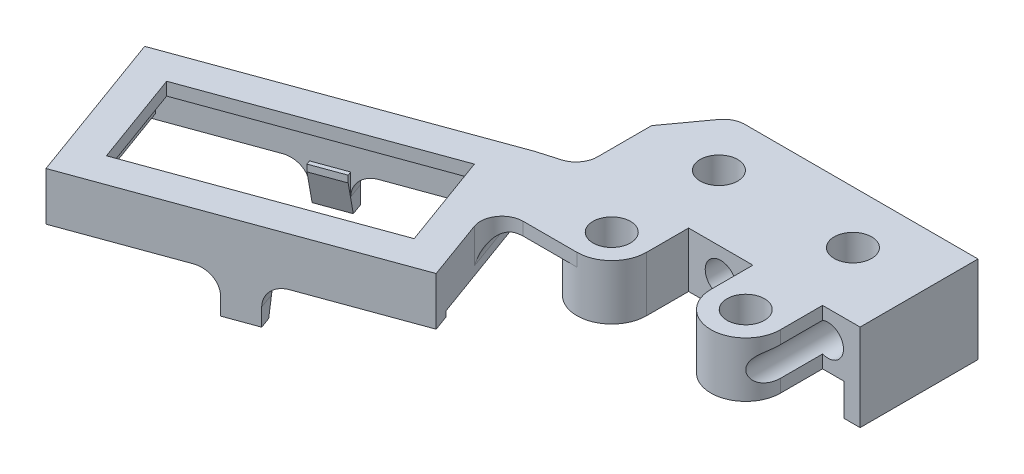
SolidWorks part; units mm, degrees
ref_plane "Front Plane" through (0, 0, 0) normal (0, 0, 1) x (1, 0, 0)
ref_plane "Top Plane" through (0, 0, 0) normal (0, 1, 0) x (1, 0, 0)
ref_plane "Right Plane" through (0, 0, 0) normal (1, 0, 0) x (0, 0, -1)
sketch "Sketch1" plane through (0, 0, 0) normal (0, 1, 0) x (1, 0, 0)
  line L5 (0, 0) -> (16.0528, 0) construction
  line L6 (0, 0) -> (0, -25.9338) construction
  line L7 (-6.25, 5) -> (-6.25, -5) construction
  line L8 (-6.25, 0) -> (0, 0) construction
  line L10 (-13, 9.92) -> (13, 9.92)
  line L11 (-13, 9.92) -> (-13, -9.92)
  line L12 (-13, -9.92) -> (13, -9.92)
  line L13 (13, 9.92) -> (13, -9.92)
  line L14 (-13, 9.92) -> (13, -9.92) construction
  line L15 (-13, -9.92) -> (13, 9.92) construction
  circle A7 centre (-6.25, 5) radius 1.75
  circle A8 centre (-6.25, -5) radius 1.75
  circle A9 centre (6.25, -5) radius 1.75
  circle A10 centre (6.25, 5) radius 1.75
  dimension "D3" = 3.5
  dimension "D4" = 12.5
  dimension "D5" = 10
  dimension "D7" = 26
  dimension "D8" = 4.92
extrude "Boss-Extrude1" add sketch "Sketch1" along normal blind 5.13 contours L13 L10 L11 L12 A9 A8 A7 A10 region at (0, 0, 0)
sketch "Sketch2" plane through (0, 0, 9.92) normal (0, 0, 1) x (1, 0, 0)
  line L0 (-13, 2.565) -> (13, 2.565) construction
  line L1 (-13, 5.13) -> (-13, 0) construction
  line L2 (13, 5.13) -> (13, 0) construction
  line L3 (0, 0) -> (0, 5.13) construction
  line L4 (-13, 5.13) -> (13, 5.13) construction
  circle A0 centre (0, 2.565) radius 1.45
  circle A1 centre (-10, 2.565) radius 1.45
  circle A2 centre (10, 2.565) radius 1.45
  dimension "D1" = 2.9
  dimension "D2" = 10
extrude "Cut-Extrude1" cut sketch "Sketch2" against normal up to next
sketch "Sketch3" plane through (0, 0, 0) normal (0, -1, 0) x (1, 0, 0)
  line L6 (-11.035, -9.92) -> (11.035, -9.92)
  line L7 (0, -9.92) -> (0, 3.71) construction
  line L8 (-13, -9.92) -> (13, -9.92) construction
  line L9 (-11.63, 3.71) -> (11.63, 3.71)
  line L10 (0, 3.71) -> (0, -9.92) construction
  line L11 (11.035, -9.92) -> (11.63, 3.71)
  line L12 (-11.035, -9.92) -> (-11.63, 3.71)
  line L13 (-10.92, 6.04) -> (10.92, 6.04)
  line L14 (0, 6.04) -> (0, -9.92) construction
  line L15 (-7.625, 12.72) -> (7.625, 12.72)
  line L16 (0, 12.72) -> (0, -9.92) construction
  line L17 (-7.625, 12.72) -> (-10.92, 6.04)
  line L18 (10.92, 6.04) -> (7.625, 12.72)
  line L19 (-9.0061, 9.92) -> (9.0061, 9.92)
  line L20 (-13, 9.92) -> (13, 9.92) construction
  line L22 (-13, 9.92) -> (13, 9.92)
  line L23 (-13, 9.92) -> (-13, -9.92)
  line L24 (-13, -9.92) -> (13, -9.92)
  line L25 (13, 9.92) -> (13, -9.92)
  spline S0 degree 2 poles (-11.63, 3.71) (-10.5122, 4.4663) (-10.92, 6.04) knots 0 0 0 1 1 1
  spline S1 degree 2 poles (11.63, 3.71) (10.5122, 4.4663) (10.92, 6.04) knots 0 0 0 1 1 1
  line M4 (13, -9.92) -> (13, 9.92)
  line M5 (13, 9.92) -> (-13, 9.92)
  line M6 (-13, 9.92) -> (-13, -9.92)
  line M7 (-13, -9.92) -> (13, -9.92)
  dimension "D8" = 22.07
  dimension "D9" = 23.26
  dimension "D11" = 13.63
  dimension "D12" = 21.84
  dimension "D14" = 2.33
  dimension "D15" = 15.25
  dimension "D17" = 6.68
extrude "Boss-Extrude2" add sketch "Sketch3" along normal blind 3 contours L12 S0 L17 M5 M6 M7 | S1 L11 L18 M7 M4 M5 region at (-11.9178, 0, 1.0165) region at (11.9178, 0, 1.0165)
sketch "Sketch4" plane through (0, -3, 0) normal (0, -1, 0) x (1, 0, 0)
  line L0 (-13, 1.08) -> (13, 1.08)
  line L1 (-13, 9.92) -> (-13, -9.92) construction
  line L2 (13, -9.92) -> (13, 9.92) construction
  line L3 (-9.5, 5) -> (-9.5, 1.08)
  line L4 (-11.035, -9.92) -> (11.035, -9.92) construction
  line L5 (-3, 5) -> (-3, 1.08)
  line L6 (3, 5) -> (3, 1.08)
  line L7 (9.5, 5) -> (9.5, 1.08)
  line L8 (-13, 1.08) -> (-13, 9.92)
  line L9 (-13, 9.92) -> (13, 9.92)
  line L10 (13, 9.92) -> (13, 1.08)
  circle A0 centre (-6.25, 5) radius 3.25
  circle A1 centre (-6.25, 5) radius 1.75 construction
  circle A2 centre (6.25, 5) radius 3.25
  spline M1 degree 2 poles (10.92, 6.04) (10.5122, 4.4663) (11.63, 3.71) knots 0 0 0 1 1 1
  line M2 (11.63, 3.71) -> (11.035, -9.92)
  line M4 (13, -9.92) -> (13, 9.92)
  line M5 (13, 9.92) -> (9.0061, 9.92)
  line M6 (9.0061, 9.92) -> (10.92, 6.04)
  dimension "D1" = 11
  dimension "D2" = 1.5
extrude "Cut-Extrude2" cut sketch "Sketch4" against normal up to next contours A2 L7 L0 L9 L8 L3 A0 L5 L6 M2 M1 M6 | L0 M2 M4 M5 M6 M1 region at (-1.8909, -3, 6.1294) region at (11.717, -3, 6.3507)
sketch "Sketch5" plane through (0, 5.13, 0) normal (0, 1, 0) x (1, 0, 0)
  line L0 (-18.8665, -2.6039) -> (-10.3647, 9.0978) construction
  line L1 (-18.8665, -2.6039) -> (-10.3647, 9.0978)
  line L2 (-8.7467, 9.9222) -> (-13, 9.92)
  line L3 (-13, 9.92) -> (-13, 5.4706)
  line L4 (-13, 9.92) -> (-13, -1.08) construction
  arc A0 (-8.7467, 9.9222) -> (-10.3647, 9.0978) centre (-8.7467, 7.9222) ccw construction
  arc A1 (-8.7467, 9.9222) -> (-10.3647, 9.0978) centre (-8.7467, 7.9222) ccw
  line M3 (13, 9.92) -> (-13, 9.92)
  line M4 (-13, 9.92) -> (-13, -1.08)
extrude "Cut-Extrude3" cut sketch "Sketch5" against normal up to next contours A1 L1 M3 M4 region at (-11.8764, 5.13, -8.4638)
sketch "Sketch6" plane through (0, 5.13, 0) normal (0, -1, 0) x (1, 0, 0)
  line L0 (-37.7857, 26.2448) -> (-11.0984, 16.5315)
  line L1 (-41.1302, 12.6701) -> (-17.262, 3.9828)
  line L2 (-41.1302, 12.6701) -> (-36.8892, 24.3223)
  line L3 (-36.8892, 24.3223) -> (-13.021, 15.6349)
  line L4 (-17.262, 3.9828) -> (-13.021, 15.6349)
  line L5 (-41.1302, 12.6701) -> (-13.021, 15.6349) construction
  line L6 (-36.8892, 24.3223) -> (-17.262, 3.9828) construction
  line L7 (-16.3655, 2.0602) -> (-11.0984, 16.5315)
  line L8 (-43.0528, 11.7736) -> (-16.3655, 2.0602)
  line L9 (-43.0528, 11.7736) -> (-37.7857, 26.2448)
  line L10 (-6.25, 8.25) -> (-14.1126, 8.25)
  line L11 (-13, 1.08) -> (-32.2548, 1.08) construction
  line L12 (-13, 1.08) -> (-46.0395, 13.1054) construction
  line L14 (-9.5, 5) -> (-9.5, 1.08) construction
  line L15 (-9.5, 5) -> (-9.5, 1.08)
  line L16 (-9.5, 1.08) -> (-13, 1.08)
  line L17 (-13, 1.08) -> (-16.3655, 2.0602)
  arc A0 (-3, 5) -> (-9.5, 5) centre (-6.25, 5) ccw construction
  arc A1 (-3, 5) -> (-9.5, 5) centre (-6.25, 5) ccw
  point P0 (-27.0756, 14.1525)
  dimension "D1" = 12.4
  dimension "D2" = 25.4
  dimension "D4" = 1.27
  dimension "D5" = 20
  dimension "D6" = 10
  dimension "D3" = 1.5
extrude "Boss-Extrude3" add sketch "Sketch6" along normal blind 1.2 contours L9 L8 L1 L2 L3 L4 L7 L0 | L1 L4 L3 L2 | A1 L10 L7 L15 region at (-24.5791, 5.13, 21.0116) region at (-12.1878, 5.13, 4.694) region at (-27.0756, 5.13, 14.1525)
sketch "Sketch9" plane through (0, 3.93, 0) normal (0, -1, 0) x (1, 0, 0)
  line L0 (-43.0528, 11.7736) -> (-37.7857, 26.2448)
  line L1 (-37.7857, 26.2448) -> (-11.0984, 16.5315)
  line L2 (-11.0984, 16.5315) -> (-16.3655, 2.0602)
  line L3 (-14.1126, 8.25) -> (-11.0984, 16.5315) construction
  line L4 (-43.0528, 11.7736) -> (-16.3655, 2.0602)
  line L5 (-43.0528, 11.7736) -> (-16.3655, 2.0602) construction
  line L6 (-41.1302, 12.6701) -> (-17.262, 3.9828)
  line L7 (-13.021, 15.6349) -> (-17.262, 3.9828)
  line L8 (-36.8892, 24.3223) -> (-13.021, 15.6349)
  line L9 (-41.1302, 12.6701) -> (-36.8892, 24.3223)
  dimension "D1" = 1.5
extrude "Boss-Extrude6" add sketch "Sketch9" along normal blind 3.3
sketch "Sketch10" plane through (0, 0.63, 0) normal (0, -1, 0) x (1, 0, 0)
  line L0 (-24.442, 21.3881) -> (-29.7092, 6.9169) construction
  line L1 (-11.0984, 16.5315) -> (-37.7857, 26.2448) construction
  line L2 (-43.0528, 11.7736) -> (-16.3655, 2.0602) construction
  line L3 (-31.1187, 7.4299) -> (-28.2996, 6.4038)
  line L4 (-31.1187, 7.4299) -> (-30.4689, 9.2153)
  line L5 (-28.2996, 6.4038) -> (-27.6498, 8.1893)
  line L6 (-30.4689, 9.2153) -> (-27.6498, 8.1893)
  line L7 (-29.0593, 8.7023) -> (-29.7092, 6.9169) construction
  line L8 (-41.1302, 12.6701) -> (-17.262, 3.9828) construction
  line L9 (-40.4192, 19.0092) -> (-13.732, 9.2958) construction
  line L10 (-37.7857, 26.2448) -> (-43.0528, 11.7736) construction
  line L11 (-16.3655, 2.0602) -> (-11.0984, 16.5315) construction
  line L12 (-25.8516, 21.9012) -> (-23.0325, 20.8751)
  line L13 (-25.8516, 21.9012) -> (-26.5014, 20.1158)
  line L14 (-26.5014, 20.1158) -> (-23.6823, 19.0897)
  line L15 (-23.0325, 20.8751) -> (-23.6823, 19.0897)
  dimension "D1" = 3
  dimension "D2" = 0.4
extrude "Boss-Extrude7" add sketch "Sketch10" along normal blind 0.8
sketch "Sketch11" plane through (0, 0.63, 0) normal (0, -1, 0) x (1, 0, 0)
  line L0 (-17.262, 3.9828) -> (-13.021, 15.6349)
  line L1 (-13.021, 15.6349) -> (-11.6114, 15.1219)
  line L2 (-16.3655, 2.0602) -> (-11.0984, 16.5315) construction
  line L3 (-11.6114, 15.1219) -> (-15.8525, 3.4697)
  line L4 (-15.8525, 3.4697) -> (-17.262, 3.9828)
  line L5 (-36.8892, 24.3223) -> (-41.1302, 12.6701)
  line L6 (-41.1302, 12.6701) -> (-42.5398, 13.1831)
  line L7 (-37.7857, 26.2448) -> (-43.0528, 11.7736) construction
  line L8 (-42.5398, 13.1831) -> (-38.2987, 24.8353)
  line L9 (-38.2987, 24.8353) -> (-36.8892, 24.3223)
extrude "Cut-Extrude4" cut sketch "Sketch11" against normal blind 0.5
sketch "Sketch12" plane through (0, 3.93, 0) normal (0, -1, 0) x (1, 0, 0)
  line L0 (-35.9927, 22.3997) -> (-39.2076, 13.5666)
  line L1 (-39.2076, 13.5666) -> (-18.1585, 5.9053)
  line L2 (-18.1585, 5.9053) -> (-14.9435, 14.7384)
  line L3 (-14.9435, 14.7384) -> (-35.9927, 22.3997)
  line L4 (-13.021, 15.6349) -> (-36.8892, 24.3223)
  line L5 (-36.8892, 24.3223) -> (-41.1302, 12.6701)
  line L6 (-41.1302, 12.6701) -> (-17.262, 3.9828)
  line L7 (-17.262, 3.9828) -> (-13.021, 15.6349)
  line L8 (-13.021, 15.6349) -> (-36.8892, 24.3223)
  line L9 (-36.8892, 24.3223) -> (-41.1302, 12.6701)
  line L10 (-41.1302, 12.6701) -> (-17.262, 3.9828)
  line L11 (-17.262, 3.9828) -> (-13.021, 15.6349)
  dimension "D1" = 0
  dimension "D2" = 1.5
extrude "Cut-Extrude5" cut sketch "Sketch12" against normal up to next contours L2 L3 L0 L1 region at (-27.0756, 3.93, 14.1525)
sketch "Sketch13" plane through (0, -0.17, 0) normal (0, -1, 0) x (1, 0, 0)
  line L6 (-30.4689, 9.2153) -> (-31.1187, 7.4299)
  line L8 (-31.1187, 7.4299) -> (-28.2996, 6.4038)
  line L10 (-28.2996, 6.4038) -> (-27.6498, 8.1893)
  line L11 (-27.6498, 8.1893) -> (-30.4689, 9.2153)
  line L12 (-30.4689, 9.2153) -> (-31.1187, 7.4299)
  line L14 (-31.1187, 7.4299) -> (-28.2996, 6.4038)
  line L16 (-28.2996, 6.4038) -> (-27.6498, 8.1893)
  line L17 (-27.6498, 8.1893) -> (-30.4689, 9.2153)
  line L19 (-25.8516, 21.9012) -> (-26.5014, 20.1158)
  line L20 (-26.5014, 20.1158) -> (-23.6823, 19.0897)
  line L21 (-23.6823, 19.0897) -> (-23.0325, 20.8751)
  line L23 (-23.0325, 20.8751) -> (-25.8516, 21.9012)
  line L25 (-25.8516, 21.9012) -> (-26.5014, 20.1158)
  line L26 (-26.5014, 20.1158) -> (-23.6823, 19.0897)
  line L27 (-23.6823, 19.0897) -> (-23.0325, 20.8751)
  line L29 (-23.0325, 20.8751) -> (-25.8516, 21.9012)
  dimension "D1" = 0
  dimension "D2" = 0
extrude "Boss-Extrude8" add sketch "Sketch13" along normal blind 2.83
fillet "Fillet1" radius 2 7 edges at (-26.1081, 0.63, 21.1964) (-23.289, 0.63, 20.1703) (-13, 4.53, 1.08) (-14.1126, 4.53, 8.25) (-15.2391, 3.93, 5.1551)
chamfer "Chamfer1" distance 3 angle 15 2 edges at (-25.0919, -3, 19.6027) (-29.0593, -3, 8.7023) first distance on face at (-25.0919, -1.185, 19.6027) first distance on face at (-29.0593, -1.185, 8.7023)
